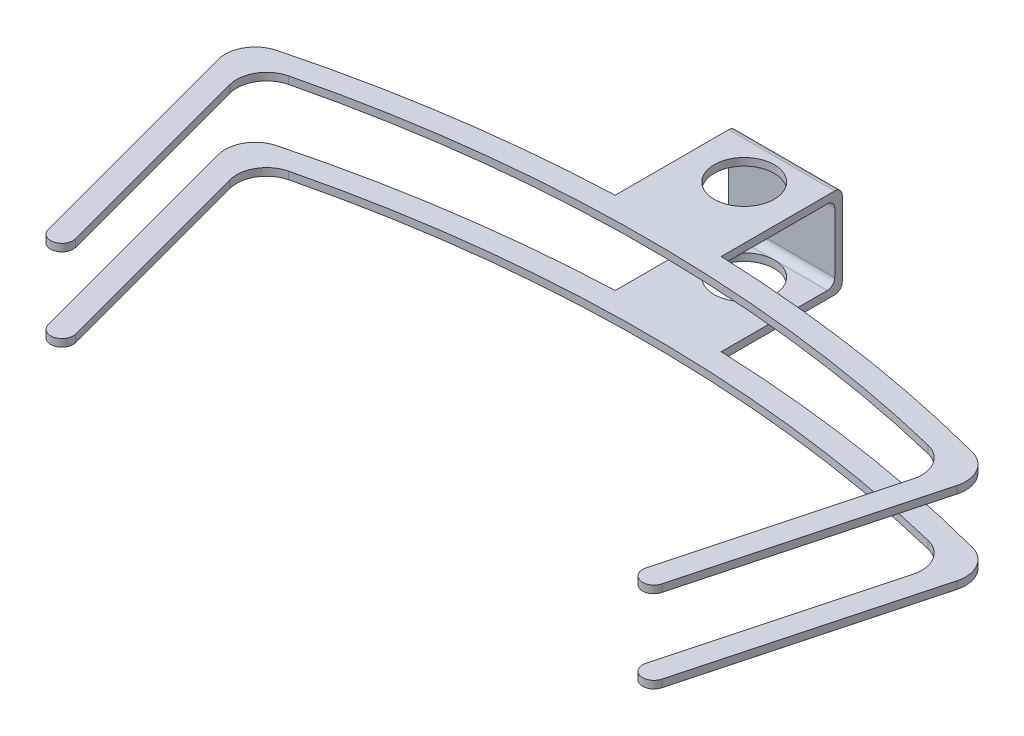
SolidWorks part; units mm, degrees
material "Plain Carbon Steel"
ref_plane "Front Plane" through (0, 0, 0) normal (0, 0, 1) x (1, 0, 0)
ref_plane "Top Plane" through (0, 0, 0) normal (0, 1, 0) x (1, 0, 0)
ref_plane "Right Plane" through (0, 0, 0) normal (1, 0, 0) x (0, 0, -1)
sketch "Sketch1" plane through (0, 0, 0) normal (0, 1, 0) x (1, 0, 0)
  line L0 (0, 0) -> (0, 99.9694) construction
  line L1 (-23.2937, 86.9333) -> (-19.2044, 71.6717) construction
  line L2 (23.2937, 86.9333) -> (19.2044, 71.6717) construction
  line L3 (-25.1276, 87.9821) -> (-20.261, 69.8196) construction
  line L4 (25.1276, 87.9821) -> (20.261, 69.8196) construction
  line L7 (23.2937, 86.9333) -> (18.8161, 70.2228)
  line L8 (-23.2937, 86.9333) -> (-18.8161, 70.2228)
  line L9 (20.261, 69.8196) -> (25.1276, 87.9821)
  line L10 (-20.261, 69.8196) -> (-25.1276, 87.9821)
  line L13 (20.261, 69.8196) -> (18.8161, 70.2228)
  line L14 (-18.8161, 70.2228) -> (-20.261, 69.8196)
  line L15 (-3.5354, 99) -> (-3.5354, 91.4317)
  line L16 (3.5354, 99) -> (3.5354, 91.4317)
  line L18 (-3.5354, 99) -> (3.5354, 99)
  circle A0 centre (0, 0) radius 90 construction
  circle A1 centre (0, 0) radius 74.2 construction
  arc A2 (23.2937, 86.9333) -> (-23.2937, 86.9333) centre (0, 0) ccw construction
  arc A3 (19.2044, 71.6717) -> (-19.2044, 71.6717) centre (0, 0) ccw construction
  arc A4 (25.1276, 87.9821) -> (3.5354, 91.4317) centre (0, 0) ccw construction
  arc A5 (20.261, 69.8196) -> (-20.261, 69.8196) centre (0, 0) ccw construction
  arc A7 (-3.5354, 91.4317) -> (-25.1276, 87.9821) centre (0, 0) ccw construction
  arc A8 (25.1276, 87.9821) -> (-25.1276, 87.9821) centre (0, 0) ccw construction
  arc A9 (-3.5354, 91.4317) -> (3.5354, 91.4317) centre (0, 0) ccw construction
  arc A10 (-23.2937, 86.9333) -> (23.2937, 86.9333) centre (0, 0) cw
  arc A11 (-25.1276, 87.9821) -> (-3.5354, 91.4317) centre (0, 0) cw
  arc A12 (25.1276, 87.9821) -> (3.5354, 91.4317) centre (0, 0) ccw
  circle A14 centre (0, 0) radius 91.5 construction
  circle A15 centre (0, 96.5) radius 2 construction
  point P7 (0, 74.2)
  point P18 (0, 91.5)
  point P22 (0, 98.5)
  point P26 (0, 96.5)
  point P33 (-3.5354, 99)
  point P34 (3.5354, 99)
  dimension "D1" = 180
  dimension "D2" = 148.4
  dimension "D5" = 7.0707
  dimension "D6" = 4
  dimension "D3" = 15
  dimension "D7" = 0.5
  dimension "D8" = 5
  dimension "D9" = 3.5354
  dimension "D4" = 1.5
extrude "Boss-Extrude1" add sketch "Sketch1" along normal blind 0.5
fillet "Fillet3" radius 2 4 edges at (-25.1276, 0.25, -87.9821) (-23.2937, 0.25, -86.9333) (25.1276, 0.25, -87.9821) (23.2937, 0.25, -86.9333)
fillet "Fillet4" 2 edges at (-18.8161, 0.25, -70.2228) (-20.261, 0.25, -69.8196) type full round first side face at (-20.7932, 0.25, -77.6012) second side face at (-22.4369, 0.25, -77.9402) middle face at (-19.5386, 0.25, -70.0212)
fillet "Fillet5" 2 edges at (18.8161, 0.25, -70.2228) (20.261, 0.25, -69.8196) type full round first side face at (20.7932, 0.25, -77.6012) second side face at (22.4369, 0.25, -77.9402) middle face at (19.5386, 0.25, -70.0212)
ref_plane "Plane1" through (0, 3, 0) normal (0, 1, 0) x (1, 0, 0)
sketch "Sketch2" plane through (3.5354, 0, 0) normal (1, 0, 0) x (0, 0, -1)
  line L0 (99, 0) -> (99.5, 0)
  line L1 (99.5, 0) -> (99.5, 3)
  line L2 (15.6774, 3) -> (-15.6774, 3) construction
  line L3 (99.5, 3) -> (99, 3)
  line L4 (99, 3) -> (99, 0)
  dimension "D1" = 0.5
extrude "Boss-Extrude2" add sketch "Sketch2" against normal up to surface (7.0707 mm away) up to face at (-3.5354, 0.25, -95.2158)
mirror "Mirror3" about plane through (0, 3, 0) normal (0, 1, 0) of "Boss-Extrude2"
mirror "Mirror5" about plane through (0, 3, 0) normal (0, 1, 0) of "Fillet5", "Fillet4", "Fillet3", "Boss-Extrude1"
fillet "Fillet7" radius 0.5 4 edges at (0, 5.5, -99) (0, 0.5, -99) (0, 0, -99.5) (0, 6, -99.5)
sketch "Sketch3" plane through (0, 6, 0) normal (0, 1, 0) x (1, 0, 0)
  point P0 (0, 96.5)
hole_wizard "Ø4.0mm Dowel Hole1" positions "Sketch3" profile "Sketch4" hole size "Ø4.0" standard "ANSI Metric" end condition through all
sketch "Sketch4" plane through (0, 6, -96.5) normal (1, 0, 0) x (0, 0, 1)
  line L0 (0, 0) -> (0, 6)
  line L1 (0, 6) -> (2, 6)
  line L2 (2, 6) -> (2, 0)
  line L5 (2, 0) -> (0, 0)
  line L11 (0, -6.35) -> (0, 107.95) construction
  dimension "Thru Hole Dia." = 4
  dimension "Thru Hole Depth" = 6
